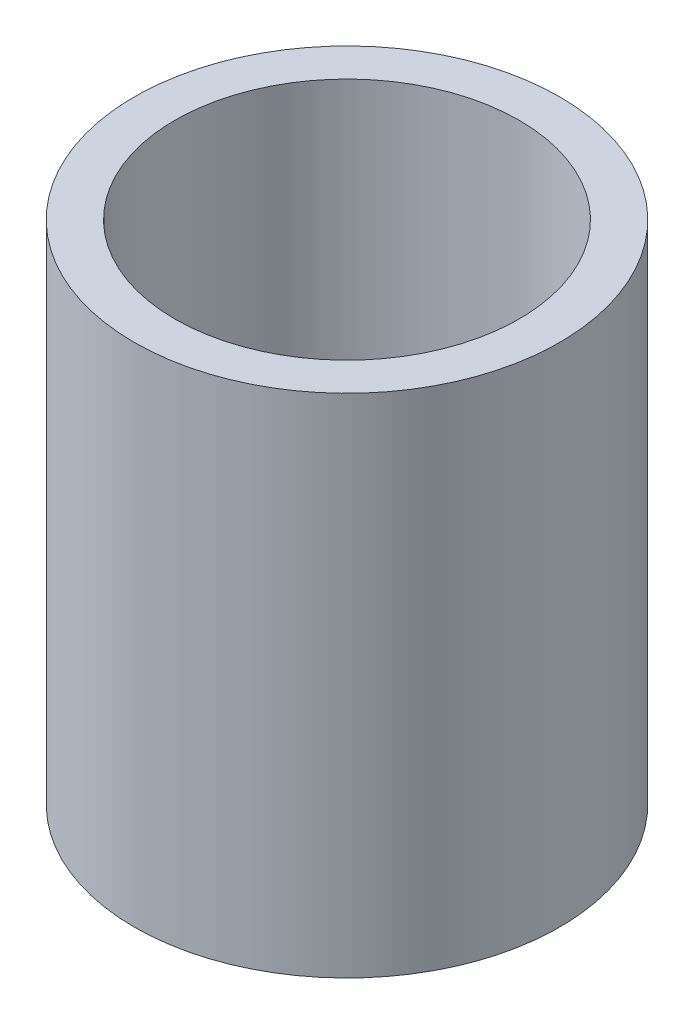
SolidWorks part; units mm, degrees
ref_plane "Front Plane" through (0, 0, 0) normal (0, 0, 1) x (1, 0, 0)
ref_plane "Top Plane" through (0, 0, 0) normal (0, 1, 0) x (1, 0, 0)
ref_plane "Right Plane" through (0, 0, 0) normal (1, 0, 0) x (0, 0, -1)
sketch "Sketch1" plane through (0, 0, 0) normal (0, 1, 0) x (1, 0, 0)
  circle A0 centre (0, 0) radius 2.55
  circle A1 centre (0, 0) radius 3.15
  dimension "D1" = 5.1
  dimension "D2" = 6.3
extrude "Boss-Extrude1" add sketch "Sketch1" along normal blind 7.5
